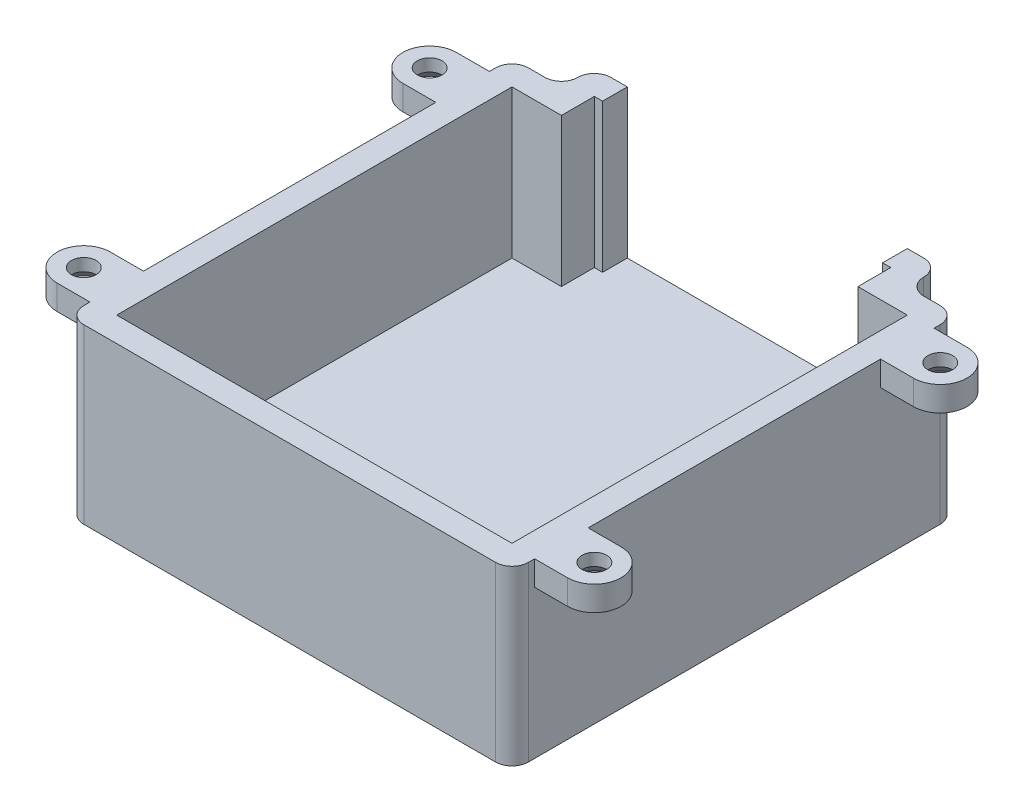
SolidWorks part; units mm, degrees
material "PLA Infill"
ref_plane "Front Plane" through (0, 0, 0) normal (0, 0, 1) x (1, 0, 0)
ref_plane "Top Plane" through (0, 0, 0) normal (0, 1, 0) x (1, 0, 0)
ref_plane "Right Plane" through (0, 0, 0) normal (1, 0, 0) x (0, 0, -1)
sketch "Sketch1" plane through (0, 0, 0) normal (0, 1, 0) x (1, 0, 0)
  line L0 (0, 54) -> (0, 0)
  line L1 (0, 0) -> (54, 0)
  line L2 (0, 0) -> (0, 58) construction
  line L3 (0, 58) -> (54, 58) construction
  line L4 (54, 0) -> (54, 58) construction
  line L5 (0, 58) -> (6, 58) construction
  line L6 (0, 58) -> (0, 54) construction
  line L7 (0, 54) -> (6, 54)
  line L8 (6, 58) -> (6, 54)
  line L9 (54, 58) -> (48, 58) construction
  line L10 (54, 58) -> (54, 54) construction
  line L11 (54, 54) -> (48, 54)
  line L12 (48, 58) -> (48, 54)
  line L13 (6, 58) -> (48, 58)
  line L14 (54, 54) -> (54, 0)
  dimension "D1" = 54
  dimension "D2" = 58
  dimension "D3" = 6
  dimension "D4" = 4
extrude "Boss-Extrude1" add sketch "Sketch1" along normal blind 21
shell "Shell2" thickness 3 removed face at (27, 21, -41.5)
sketch "Sketch2" plane through (0, 0, -58) normal (0, 0, -1) x (-1, 0, 0)
  line L1 (-44, 3) -> (-10, 3)
  line L2 (-44, 3) -> (-44, 21)
  line L3 (-44, 21) -> (-10, 21)
  line L4 (-10, 3) -> (-10, 21)
  line L7 (-27, 0) -> (-27, 21) construction
  line L9 (-48, 21) -> (-6, 21) construction
  line L10 (-48, 0) -> (-6, 0) construction
  point P10 (-27, 3)
  dimension "D1" = 18
  dimension "D2" = 34
extrude "Cut-Extrude1" cut sketch "Sketch2" against normal up to surface (3 mm away) up to face at (27, 12, -55)
fillet "Fillet2" radius 2 8 edges at (6, 10.5, -58) (6, 10.5, -54) (0, 10.5, -54) (0, 10.5, 0) (54, 10.5, 0) (48, 10.5, -54) (48, 10.5, -58) (54, 10.5, -54)
sketch "Sketch4" plane through (0, 21, 0) normal (0, 1, 0) x (1, 0, 0)
  line L0 (27, -1000) -> (27, 49000) construction
  line L1 (2, 0) -> (52, 0) construction
  line L2 (0, 52) -> (0, 2) construction
  line L7 (-7.25, 48) -> (0, 48) construction
  line L8 (0, 51.25) -> (-7.25, 51.25) construction
  line L9 (0, 51.25) -> (0, 44.75)
  line L10 (0, 44.75) -> (-7.25, 44.75) construction
  line L11 (-7.25, 51.25) -> (-7.25, 44.75) construction
  line L12 (-4, 51.25) -> (0, 51.25)
  line L13 (-4, 44.75) -> (0, 44.75)
  line L14 (-1000, 27) -> (49000, 27) construction
  line L15 (-4, 2.75) -> (0, 2.75)
  line L16 (0, 2.75) -> (0, 9.25)
  line L17 (-4, 9.25) -> (0, 9.25)
  line L18 (58, 9.25) -> (54, 9.25)
  line L19 (54, 2.75) -> (54, 9.25)
  line L20 (58, 2.75) -> (54, 2.75)
  line L21 (58, 51.25) -> (54, 51.25)
  line L22 (54, 51.25) -> (54, 44.75)
  line L23 (58, 44.75) -> (54, 44.75)
  circle A0 centre (-4, 48) radius 1.5
  arc A1 (-4, 44.75) -> (-4, 51.25) centre (-4, 48) cw
  circle A2 centre (-4, 6) radius 1.5
  arc A3 (-4, 9.25) -> (-4, 2.75) centre (-4, 6) ccw
  arc A4 (58, 9.25) -> (58, 2.75) centre (58, 6) cw
  circle A5 centre (58, 6) radius 1.5
  circle A6 centre (58, 48) radius 1.5
  arc A7 (58, 44.75) -> (58, 51.25) centre (58, 48) ccw
  point P5 (27, 0)
  point P23 (0, 27)
  dimension "D1" = 3
  dimension "D2" = 6.5
  dimension "D3" = 48
  dimension "D4" = 4
extrude "Boss-Extrude2" add sketch "Sketch4" against normal blind 3
chamfer "Chamfer1" distance 1.5 angle 45 4 edges at (-4, 18, -46.5) (-4, 18, -7.5) (58, 18, -4.5) (58, 18, -49.5)
